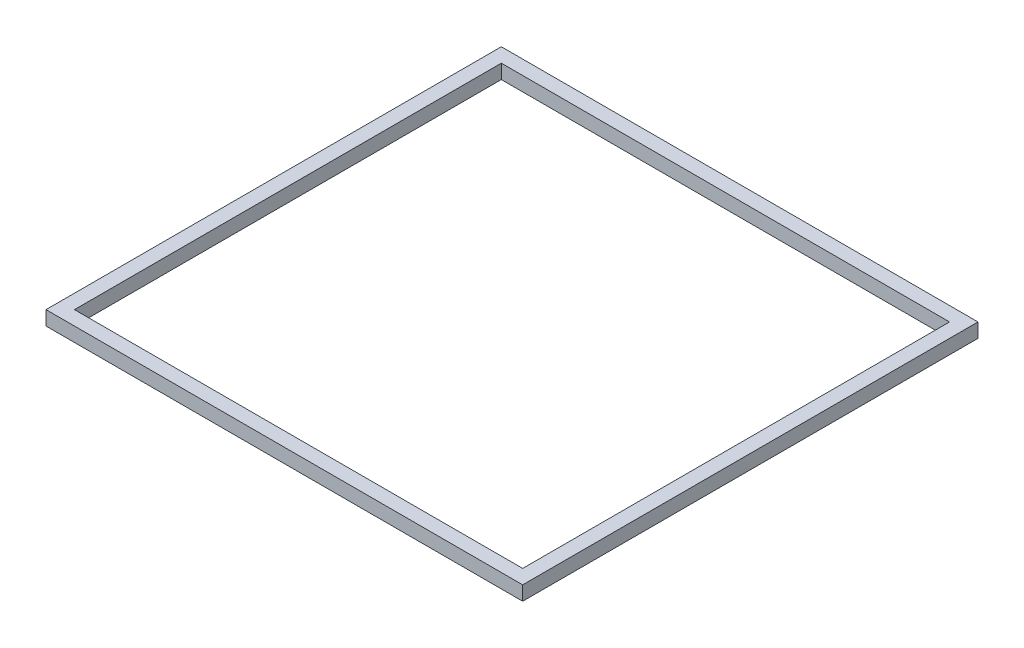
SolidWorks part; units mm, degrees
material "6061 合金"
ref_plane "前视基准面" through (0, 0, 0) normal (0, 0, 1) x (1, 0, 0)
ref_plane "上视基准面" through (0, 0, 0) normal (0, 1, 0) x (1, 0, 0)
ref_plane "右视基准面" through (0, 0, 0) normal (1, 0, 0) x (0, 0, -1)
sketch "草图1" plane through (0, 0, 0) normal (0, 1, 0) x (1, 0, 0)
  line L1 (-329.3879, 147.905) -> (340.6121, 147.905)
  line L2 (-329.3879, 147.905) -> (-329.3879, -492.095)
  line L3 (-329.3879, -492.095) -> (340.6121, -492.095)
  line L4 (340.6121, 147.905) -> (340.6121, -492.095)
  line L5 (-309.3879, 127.905) -> (320.6121, 127.905)
  line L6 (-309.3879, 127.905) -> (-309.3879, -472.095)
  line L7 (-309.3879, -472.095) -> (320.6121, -472.095)
  line L8 (320.6121, 127.905) -> (320.6121, -472.095)
  dimension "D1" = 670
  dimension "D2" = 640
  dimension "D3" = 20
  dimension "D4" = 20
  dimension "D5" = 20
  dimension "D6" = 20
extrude "凸台-拉伸1" add sketch "草图1" along normal blind 20
